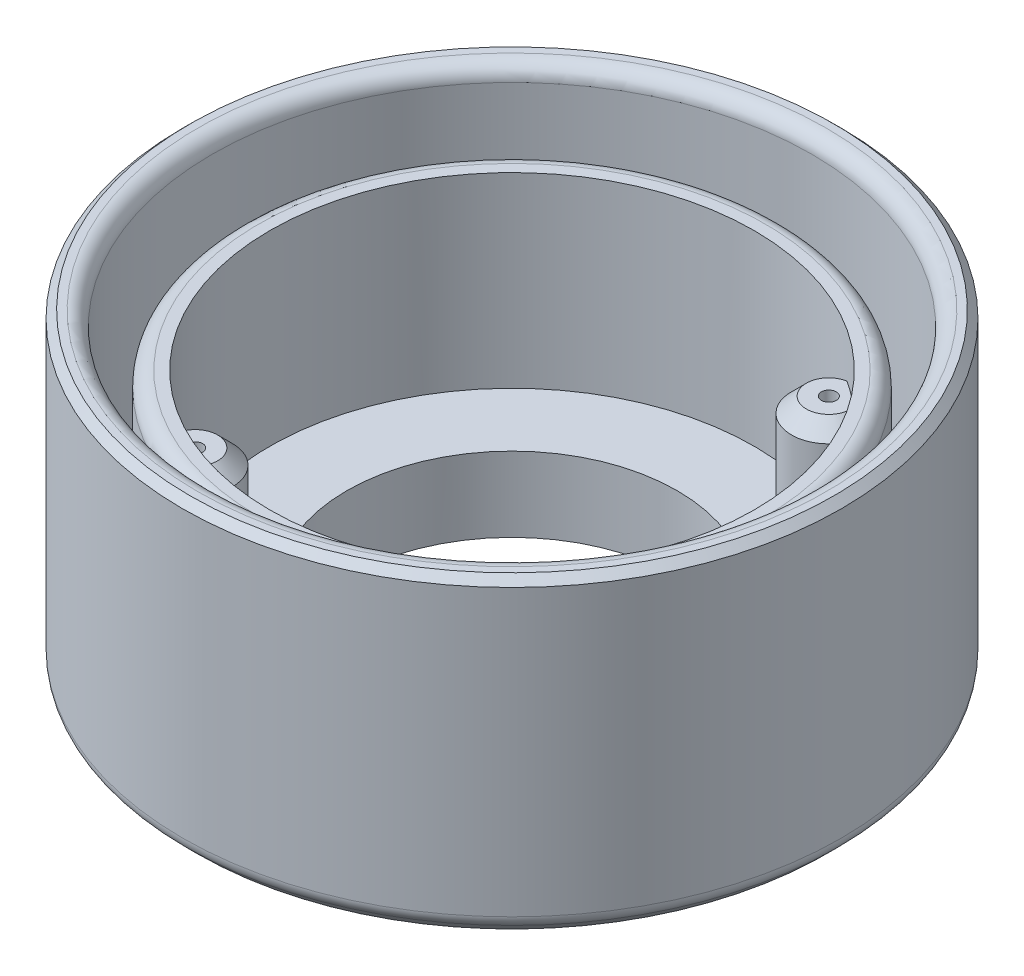
SolidWorks part; units mm, degrees
ref_plane "Alzado" through (0, 0, 0) normal (0, 0, 1) x (1, 0, 0)
ref_plane "Planta" through (0, 0, 0) normal (0, 1, 0) x (1, 0, 0)
ref_plane "Vista lateral" through (0, 0, 0) normal (1, 0, 0) x (0, 0, -1)
sketch "Croquis1" plane through (0, 0, 0) normal (0, 1, 0) x (1, 0, 0)
  circle A0 centre (0, 0) radius 17.95
  circle A1 centre (0, 0) radius 20.05
  circle A2 centre (0, 0) radius 22.05
  circle A3 centre (0, 0) radius 16.2
  dimension "D1" = 35.9
  dimension "D2" = 1.75
  dimension "D3" = 40.1
  dimension "D4" = 2
extrude "Saliente-Extruir1" add sketch "Croquis1" along normal blind 16 contours A2 A1 region at (-21.4263, 0, 0)
extrude "Saliente-Extruir2" add sketch "Croquis1<4>" along normal blind 12.5 separate body contours A0 A3 region at (-17.4423, 0, 0)
sketch "Croquis1<4>" plane through (0, 0, 0) normal (0, 1, 0) x (1, 0, 0) same geometry as "Croquis1"
extrude "Saliente-Extruir4" add sketch "Croquis1<6>" against normal blind 5 contours A3 | A0 A3 | A1 A0 | A2 A1 region at (-17.4423, 0, 0) region at (-19.4829, 0, 0) region at (-21.4263, 0, 0) region at (0, 0, 0)
sketch "Croquis1<6>" plane through (0, 0, 0) normal (0, 1, 0) x (1, 0, 0) same geometry as "Croquis1"
sketch "Croquis4" plane through (0, -5, 0) normal (0, -1, 0) x (1, 0, 0)
  line L0 (-9.1, 12.1) -> (0, 0) construction
  line L1 (0, 0) -> (9.1, -12.1) construction
  line L3 (13, 16) -> (-13, 16) construction
  line L4 (13, 16) -> (13, -16) construction
  line L5 (13, -16) -> (-13, -16) construction
  line L6 (-13, 16) -> (-13, -16) construction
  line L7 (13, 16) -> (-13, -16) construction
  line L8 (13, -16) -> (-13, 16) construction
  circle A0 centre (0, 0) radius 11.05
  circle A1 centre (-9.1, 12.1) radius 0.5
  circle A2 centre (9.1, -12.1) radius 0.5
  point P11 (-9.1, 12.6)
  point P12 (-9.6, 12.1)
  dimension "D1" = 22.1
  dimension "D4" = 1
  dimension "D2" = 26
  dimension "D3" = 32
  dimension "D5" = 3.9
  dimension "D6" = 3.9
extrude "Cortar-Extruir1" cut sketch "Croquis4" against normal up to next
sketch "Croquis5" plane through (0, -5, 0) normal (0, -1, 0) x (1, 0, 0)
  circle A0 centre (-9.1, 12.1) radius 0.5 construction
  circle A1 centre (9.1, -12.1) radius 0.5 construction
  circle A2 centre (-9.1, 12.1) radius 0.5
  circle A3 centre (9.1, -12.1) radius 0.5
  circle A4 centre (-9.1, 12.1) radius 2.5
  circle A5 centre (9.1, -12.1) radius 2.5
  dimension "D1" = 5
extrude "Cortar-Extruir2" cut sketch "Croquis5" against normal blind 4.5
sketch "Croquis6" plane through (0, -0.5, 0) normal (0, -1, 0) x (1, 0, 0)
  circle A0 centre (-9.1, 12.1) radius 2.5 construction
  circle A1 centre (9.1, -12.1) radius 2.5 construction
  circle A2 centre (-9.1, 12.1) radius 2.5
  circle A3 centre (9.1, -12.1) radius 2.5
  circle A4 centre (-9.1, 12.1) radius 0.5 construction
  circle A5 centre (-9.1, 12.1) radius 0.5
  circle A6 centre (9.1, -12.1) radius 0.5 construction
  circle A7 centre (9.1, -12.1) radius 0.5
extrude "Saliente-Extruir5" add sketch "Croquis6" against normal blind 10
fillet "Redondeo2" radius 1 2 edges at (0, 12.5, 17.95) (0, 16, 20.05)
chamfer "Chaflán1" distance 1 angle 45 5 edges at (0, -5, 22.05) (-9.1, -5, 9.6) (9.1, -5, -14.6) (7.5974, 9.5, -10.102) (-7.5974, 9.5, 10.102)
fillet "Redondeo3" radius 1 1 edges at (0, -4, 22.05)
chamfer "Chaflán2" distance 0.5 angle 45 1 edges at (0, 16, 22.05)
chamfer "Chaflán3" distance 2 angle 30 2 edges at (9.1, -0.5, -12.6) (-9.1, -0.5, 11.6) first distance on face at (9.1, -0.5, -12.6) first distance on face at (-9.1, -0.5, 11.6)
